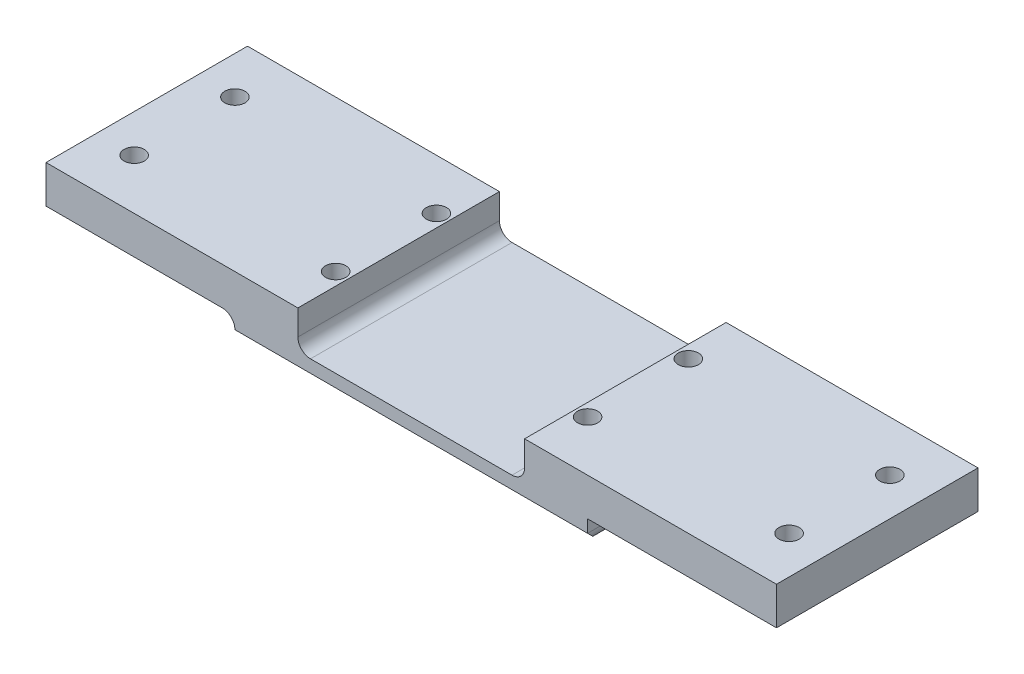
SolidWorks part; units mm, degrees
ref_plane "Front Plane" through (0, 0, 0) normal (0, 0, 1) x (1, 0, 0)
ref_plane "Top Plane" through (0, 0, 0) normal (0, 1, 0) x (1, 0, 0)
ref_plane "Right Plane" through (0, 0, 0) normal (1, 0, 0) x (0, 0, -1)
sketch "Sketch1" plane through (0, 0, 0) normal (0, 1, 0) x (1, 0, 0)
  line L1 (0, 0) -> (184.15, 0)
  line L2 (0, 0) -> (0, 50.8)
  line L3 (0, 50.8) -> (184.15, 50.8)
  line L4 (184.15, 0) -> (184.15, 50.8)
  dimension "D1" = 184.15
  dimension "D2" = 50.8
extrude "Boss-Extrude1" add sketch "Sketch1" along normal blind 9.525
sketch "Sketch4" plane through (0, 0, 0) normal (0, 0, 1) x (1, 0, 0)
  line L0 (0, 0) -> (184.15, 0) construction
  line L1 (47.625, 0) -> (136.525, 0)
  line L2 (47.625, 0) -> (47.625, -6.35)
  line L3 (47.625, -6.35) -> (136.525, -6.35)
  line L4 (136.525, 0) -> (136.525, -6.35)
  line L5 (92.075, 9.525) -> (92.075, -52.0257) construction
  line L6 (0, 9.525) -> (184.15, 9.525) construction
  dimension "D1" = 88.9
  dimension "D2" = 6.35
extrude "Boss-Extrude2" add sketch "Sketch4" against normal up to surface (50.8 mm away) up to face at (92.075, 4.7625, -50.8)
sketch "Sketch5" plane through (0, 9.525, 0) normal (0, 1, 0) x (1, 0, 0)
  line L0 (184.15, 50.8) -> (0, 50.8) construction
  line L1 (120.65, 50.8) -> (63.5, 50.8)
  line L2 (120.65, 50.8) -> (120.65, 0)
  line L3 (120.65, 0) -> (63.5, 0)
  line L4 (63.5, 50.8) -> (63.5, 0)
  line L5 (0, 0) -> (184.15, 0) construction
  line L6 (92.075, 50.8) -> (92.075, -25.2417) construction
  dimension "D1" = 57.15
extrude "Cut-Extrude1" cut sketch "Sketch5" against normal blind 9.525
hole_wizard "#10 Clearance Hole1" positions "Sketch2" profile "Sketch3" hole size "#10" standard "ANSI Inch" end condition up to next
sketch "Sketch2" plane through (0, 9.525, 0) normal (0, 1, 0) x (1, 0, 0)
  line L0 (0, 50.8) -> (0, 0) construction
  line L1 (184.15, 50.8) -> (120.65, 50.8) construction
  line L2 (0, 0) -> (63.5, 0) construction
  line L3 (184.15, 0) -> (184.15, 50.8) construction
  point P0 (9.525, 38.1)
  point P2 (9.525, 12.7)
  point P4 (60.325, 12.7)
  point P6 (60.325, 38.1)
  point P8 (123.825, 38.1)
  point P10 (123.825, 12.7)
  point P12 (174.625, 12.7)
  point P14 (174.625, 38.1)
  dimension "D1" = 9.525
  dimension "D2" = 12.7
  dimension "D3" = 9.525
  dimension "D4" = 12.7
  dimension "D5" = 12.7
  dimension "D6" = 50.8
  dimension "D7" = 12.7
  dimension "D8" = 50.8
  dimension "D9" = 12.7
  dimension "D10" = 9.525
  dimension "D11" = 12.7
  dimension "D12" = 9.525
  dimension "D13" = 50.8
  dimension "D14" = 12.7
  dimension "D15" = 12.7
  dimension "D16" = 50.8
sketch "Sketch3" plane through (9.525, 9.525, -38.1) normal (1, 0, 0) x (0, 0, 1)
  line L0 (0, 0) -> (0, 9.525)
  line L1 (0, 9.525) -> (2.5527, 9.525)
  line L2 (2.5527, 9.525) -> (2.5527, 0)
  line L5 (2.5527, 0) -> (0, 0)
  line L11 (0, -6.35) -> (0, 107.95) construction
  dimension "Thru Hole Dia." = 5.1054
  dimension "Thru Hole Depth" = 9.525
fillet "Fillet1" radius 3.175 5 edges at (47.625, 0, -25.4) (47.625, -6.35, -25.4) (136.525, -6.35, -25.4) (63.5, 0, -25.4) (120.65, 0, -25.4)
chamfer "Chamfer1" distance 3.175 angle 45 1 edges at (92.075, -6.35, 0) tangent propagation no
ref_plane "Plane1" through (92.075, 0, 0) normal (-1, 0, 0) x (0, 0, 1)
